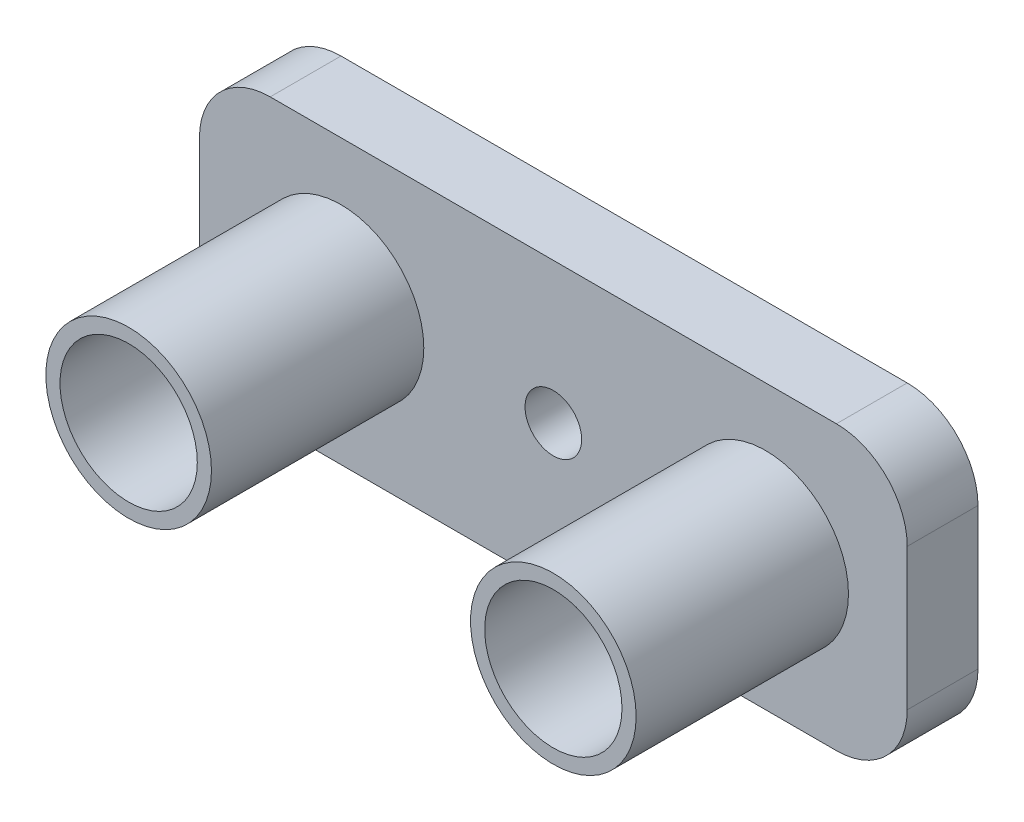
SolidWorks part; units mm, degrees
note: The reader was unsure of these and kept them because the rebuilt part matched: shared geometry of "Sketch1<4>".
ref_plane "Front Plane" through (0, 0, 0) normal (0, 0, 1) x (1, 0, 0)
ref_plane "Top Plane" through (0, 0, 0) normal (0, 1, 0) x (1, 0, 0)
ref_plane "Right Plane" through (0, 0, 0) normal (1, 0, 0) x (0, 0, -1)
sketch "Sketch1" plane through (0, 0, 0) normal (0, 0, 1) x (1, 0, 0)
  line L0 (-2.0303, 9.119) -> (47.9697, 9.0455) construction
  line L1 (2.9697, 19.0455) -> (42.9697, 19.0455)
  line L2 (-2.0303, 14.0455) -> (-2.0303, 4.1925)
  line L3 (3.1168, -0.9545) -> (42.9697, -0.9545)
  line L4 (47.9697, 14.0455) -> (47.9697, 4.0455)
  line L5 (22.9697, 19.0455) -> (22.9697, -2.1253) construction
  arc A0 (-2.0303, 14.0455) -> (2.9697, 19.0455) centre (2.9697, 14.0455) cw
  arc A1 (47.9697, 14.0455) -> (42.9697, 19.0455) centre (42.9697, 14.0455) ccw
  arc A2 (47.9697, 4.0455) -> (42.9697, -0.9545) centre (42.9697, 4.0455) cw
  arc A3 (3.1168, -0.9545) -> (-2.0303, 4.1925) centre (3.1168, 4.1925) cw
  circle A4 centre (7.9697, 9.1043) radius 4.85
  circle A5 centre (37.9697, 9.0602) radius 4.85
  circle A6 centre (22.9697, 9.0822) radius 2
  point P6 (-2.0303, 19.0455)
  point P9 (47.9697, 19.0455)
  point P14 (-2.0303, -0.9545)
  point P25 (0, 0)
  dimension "D3" = 5
  dimension "D4" = 5
  dimension "D5" = 5
  dimension "D6" = 5.1471
  dimension "D9" = 9.7
  dimension "D10" = 9.7
  dimension "D1" = 20
  dimension "D2" = 50
  dimension "D7" = 10
  dimension "D8" = 10
extrude "Boss-Extrude1" add sketch "Sketch1" along normal blind 5 contours L0 L2 A3 L3 A2 L4 A5 A4 | L2 L0 A4 A5 L4 A1 L1 A0
extrude "Extrude-Thin1" add sketch "Sketch1<4>" along normal blind 20 thin contours A4 | A5
sketch "Sketch1<4>" plane through (0, 0, 0) normal (0, 0, 1) x (1, 0, 0) same geometry as "Sketch1"
